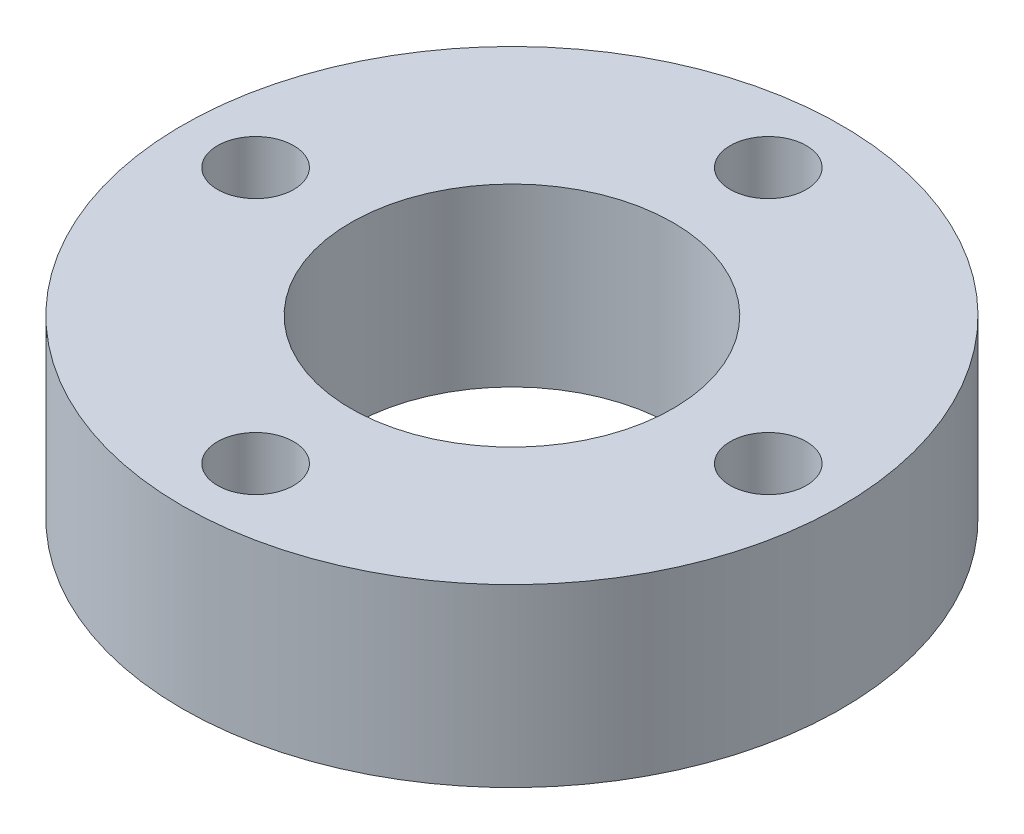
SolidWorks part; units mm, degrees
ref_plane "前视基准面" through (0, 0, 0) normal (0, 0, 1) x (1, 0, 0)
ref_plane "上视基准面" through (0, 0, 0) normal (0, 1, 0) x (1, 0, 0)
ref_plane "右视基准面" through (0, 0, 0) normal (1, 0, 0) x (0, 0, -1)
other "Configuration Table"
sketch "草图1" plane through (0, 0, 0) normal (0, 1, 0) x (1, 0, 0)
  circle A0 centre (0, 0) radius 22.5
  dimension "D1" = 45
extrude "凸台-拉伸1" add sketch "草图1" along normal blind 12
sketch "草图2" plane through (0, 0, 0) normal (0, -1, 0) x (1, 0, 0)
  circle A0 centre (0, 0) radius 17.5
  circle A1 centre (17.5, 0) radius 4.2
  circle A2 centre (0, 17.5) radius 4.2
  circle A3 centre (-17.5, 0) radius 4.2
  circle A4 centre (0, -17.5) radius 4.2
  dimension "D1" = 35
  dimension "D2" = 8.4
  dimension "D3" = 8.4
  dimension "D4" = 8.4
  dimension "D5" = 8.4
extrude "切除-拉伸1" cut sketch "草图2" against normal blind 4.4 contours A0 A1 | A0 A1 | A0 A4 | A0 A4 | A0 A3 | A0 A2 | A0 A2 | A3 region at (15.6298, 0, 0) region at (19.1887, 0, 0) region at (0, 0, 15.6298) region at (0, 0, 19.1887) region at (0, 0, -19.1887) region at (0, 0, -15.6298) region at (-15.6298, 0, 0)
sketch "草图3" plane through (0, 0, 0) normal (0, -1, 0) x (1, 0, 0)
  circle A0 centre (0, 17.5) radius 2.6
  circle A1 centre (17.5, 0) radius 2.6
  circle A2 centre (0, -17.5) radius 2.6
  circle A3 centre (-17.5, 0) radius 2.6
  dimension "D1" = 5.2
  dimension "D2" = 5.2
  dimension "D3" = 5.2
  dimension "D4" = 5.2
extrude "切除-拉伸2" cut sketch "草图3" against normal through all
sketch "草图4" plane through (0, 0, 0) normal (0, -1, 0) x (1, 0, 0)
  circle A0 centre (0, 0) radius 4
  dimension "D1" = 8
extrude "切除-拉伸3" cut sketch "草图4" against normal through all
sketch "草图5" plane through (0, 0, 0) normal (0, -1, 0) x (1, 0, 0)
  circle A0 centre (0, 0) radius 11
  dimension "D1" = 22
extrude "切除-拉伸4" cut sketch "草图5" against normal through all
